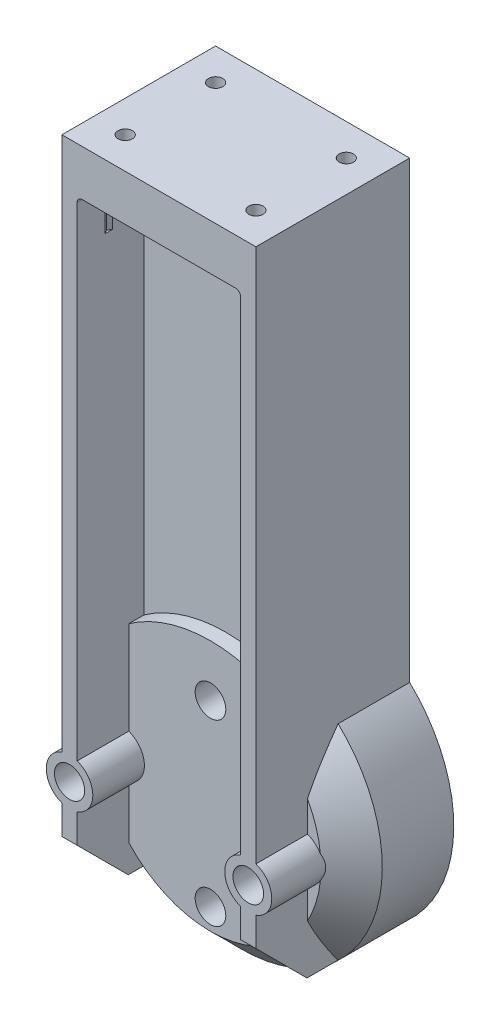
SolidWorks part; units mm, degrees
ref_plane "Front Plane" through (0, 0, 0) normal (0, 0, 1) x (1, 0, 0)
ref_plane "Top Plane" through (0, 0, 0) normal (0, 1, 0) x (1, 0, 0)
ref_plane "Right Plane" through (0, 0, 0) normal (1, 0, 0) x (0, 0, -1)
sketch "Sketch1" plane through (0, 0, 0) normal (0, 0, 1) x (1, 0, 0)
  circle A0 centre (0, 0) radius 35.1028
extrude "Boss-Extrude1" add sketch "Sketch1" along normal blind 25.4
sketch "Sketch2" plane through (0, 0, 0) normal (0, 1, 0) x (1, 0, 0)
  line L0 (0, -38.227) -> (0, 0) construction
  line L1 (-24.13, 0) -> (-20.32, 0)
  line L2 (35.1028, 0) -> (-35.1028, 0) construction
  line L3 (24.13, 0) -> (24.13, -38.227)
  line L4 (-24.13, 0) -> (-24.13, -38.227)
  line L5 (24.13, -38.227) -> (20.32, -38.227)
  line L13 (20.32, 0) -> (24.13, 0)
  line L14 (-20.32, -38.227) -> (-24.13, -38.227)
  line L15 (-24.13, -19.1135) -> (24.13, -19.1135) construction
  line L16 (-20.32, -38.227) -> (-20.32, -21.6535)
  line L17 (-20.32, -21.6535) -> (20.32, -21.6535)
  line L18 (20.32, -38.227) -> (20.32, -21.6535)
  line L19 (20.32, 0) -> (20.32, -16.5735)
  line L20 (-20.32, 0) -> (-20.32, -16.5735)
  line L21 (-20.32, -16.5735) -> (20.32, -16.5735)
  point P9 (0, -21.6535)
  point P14 (0, -8.89)
  point P18 (0, -21.6535)
  point P19 (0, -13.97)
  dimension "D1" = 48.26
  dimension "D2" = 3.81
  dimension "D3" = 2.54
  dimension "D5" = 38.227
extrude "Boss-Extrude2" add sketch "Sketch2" along normal blind 127 and the other way blind 25.4
chamfer "Chamfer1" distance 7.62 angle 45 1 edges at (0, -35.1028, 25.4)
chamfer "Chamfer3" distance 12.7 angle 45 2 edges at (22.225, -25.4, 38.227) (-22.225, -25.4, 38.227)
sketch "Sketch3" plane through (0, 127, 0) normal (0, 1, 0) x (1, 0, 0)
  line L0 (0, 0) -> (0, -38.227) construction
  line L1 (-24.13, -38.227) -> (24.13, -38.227)
  line L2 (-24.13, -38.227) -> (-24.13, 0)
  line L3 (-24.13, 0) -> (24.13, 0)
  line L4 (24.13, -38.227) -> (24.13, 0)
  line L5 (-24.13, -19.1135) -> (24.13, -19.1135) construction
  circle A0 centre (16.256, -30.353) radius 1.778
  circle A1 centre (-16.256, -30.353) radius 1.778
  circle A2 centre (16.256, -7.874) radius 1.778
  circle A3 centre (-16.256, -7.874) radius 1.778
  dimension "D1" = 3.556
  dimension "D2" = 7.874
  dimension "D3" = 7.874
extrude "Boss-Extrude3" add sketch "Sketch3" along normal blind 11.43
sketch "Sketch4" plane through (0, 127, 0) normal (0, -1, 0) x (1, 0, 0)
  line L1 (-11.6366, 30.353) -> (-13.9463, 34.3535)
  line L2 (-13.9463, 34.3535) -> (-18.5657, 34.3535)
  line L3 (-18.5657, 34.3535) -> (-20.8754, 30.353)
  line L4 (-20.8754, 30.353) -> (-18.5657, 26.3525)
  line L5 (-18.5657, 26.3525) -> (-13.9463, 26.3525)
  line L6 (-13.9463, 26.3525) -> (-11.6366, 30.353)
  line L7 (-11.6366, 7.874) -> (-13.9463, 11.8745)
  line L8 (-13.9463, 11.8745) -> (-18.5657, 11.8745)
  line L9 (-18.5657, 11.8745) -> (-20.8754, 7.874)
  line L10 (-20.8754, 7.874) -> (-18.5657, 3.8735)
  line L11 (-18.5657, 3.8735) -> (-13.9463, 3.8735)
  line L12 (-13.9463, 3.8735) -> (-11.6366, 7.874)
  line L13 (11.6366, 30.353) -> (13.9463, 26.3525)
  line L14 (13.9463, 26.3525) -> (18.5657, 26.3525)
  line L15 (18.5657, 26.3525) -> (20.8754, 30.353)
  line L16 (20.8754, 30.353) -> (18.5657, 34.3535)
  line L17 (18.5657, 34.3535) -> (13.9463, 34.3535)
  line L18 (13.9463, 34.3535) -> (11.6366, 30.353)
  line L19 (11.6366, 7.874) -> (13.9463, 3.8735)
  line L20 (13.9463, 3.8735) -> (18.5657, 3.8735)
  line L21 (18.5657, 3.8735) -> (20.8754, 7.874)
  line L22 (20.8754, 7.874) -> (18.5657, 11.8745)
  line L23 (18.5657, 11.8745) -> (13.9463, 11.8745)
  line L24 (13.9463, 11.8745) -> (11.6366, 7.874)
  circle A0 centre (-16.256, 30.353) radius 4.0005 construction
  circle A1 centre (-16.256, 7.874) radius 4.0005 construction
  circle A2 centre (16.256, 30.353) radius 4.0005 construction
  circle A3 centre (16.256, 7.874) radius 4.0005 construction
  dimension "D1" = 8.001
  dimension "D2" = 8.001
  dimension "D3" = 8.001
  dimension "D4" = 8.001
extrude "Cut-Extrude1" cut sketch "Sketch4" against normal blind 6.35 and the other way blind 11.43
sketch "Sketch5" plane through (0, 0, 0) normal (0, 0, -1) x (-1, 0, 0)
  circle A0 centre (0, 22.225) radius 1.9685
  circle A1 centre (22.225, 0) radius 1.9685
  circle A2 centre (0, -22.225) radius 1.9685
  circle A3 centre (-22.225, 0) radius 1.9685
extrude "Cut-Extrude2" cut sketch "Sketch5" against normal through all
sketch "Sketch6" plane through (0, 0, 25.4) normal (0, 0, 1) x (1, 0, 0)
  circle A0 centre (0, 22.225) radius 3.81
  circle A1 centre (22.225, 0) radius 3.81
  circle A2 centre (0, -22.225) radius 3.81
  circle A3 centre (-22.225, 0) radius 3.81
  dimension "D1" = 7.62
  dimension "D2" = 7.62
  dimension "D3" = 7.62
  dimension "D4" = 7.62
extrude "Cut-Extrude3" cut sketch "Sketch6" along normal through all and the other way blind 12.7
sketch "Sketch7" plane through (0, 0, 25.4) normal (0, 0, 1) x (1, 0, 0)
  circle A0 centre (-22.225, 0) radius 3.7597
  circle A2 centre (22.225, 0) radius 3.81
  circle A6 centre (-22.225, 0) radius 5.7917
  circle A7 centre (22.225, 0) radius 5.842
  dimension "D1" = 2.032
extrude "Boss-Extrude4" add sketch "Sketch7" along normal up to surface (12.827 mm away) and the other way through all up to face at (22.225, -8.1274, 38.227)
fillet "Fillet1" radius 1.27 10 edges at (20.32, 127, 3.456) (20.32, 127, 12.7047) (0, 127, 16.5735) (-20.32, 127, 12.7047) (-20.32, 127, 3.456) (20.32, 127, 34.771) (20.32, 127, 25.5223) (-20.32, 127, 34.771) (-20.32, 127, 25.5223) (0, 127, 21.6535)
